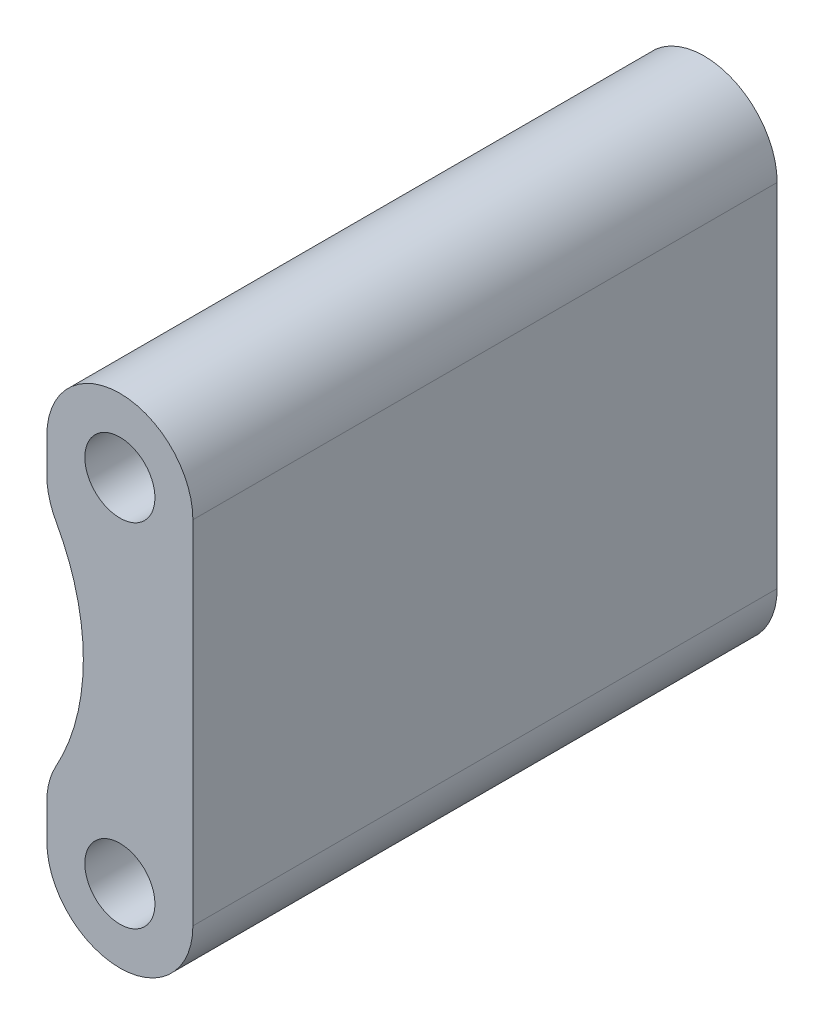
SolidWorks part; units mm, degrees
ref_plane "Front Plane" through (0, 0, 0) normal (0, 0, 1) x (1, 0, 0)
ref_plane "Top Plane" through (0, 0, 0) normal (0, 1, 0) x (1, 0, 0)
ref_plane "Right Plane" through (0, 0, 0) normal (1, 0, 0) x (0, 0, -1)
sketch "Sketch1" plane through (0, 0, 0) normal (0, 0, 1) x (1, 0, 0)
  line L0 (0, 22.9362) -> (0, 0) construction
  line L1 (0, 22.9362) -> (0, 0) construction
  line L2 (4.7625, 22.9362) -> (4.7625, 0)
  line L3 (-4.7625, 22.9362) -> (-4.7625, 0)
  circle A0 centre (0, 0) radius 2.286
  circle A1 centre (0, 22.9362) radius 2.286
  arc A2 (4.7625, 22.9362) -> (-4.7625, 22.9362) centre (0, 22.9362) ccw
  arc A3 (-4.7625, 0) -> (4.7625, 0) centre (0, 0) ccw
  point P5 (0, 11.4681)
  dimension "D1" = 4.572
  dimension "D3" = 4.7625
  dimension "D2" = 22.9362
extrude "Boss-Extrude1" add sketch "Sketch1" along normal blind 38.1
sketch "Sketch2" plane through (0, 0, 38.1) normal (0, 0, 1) x (1, 0, 0)
  line L0 (-4.7625, 22.9362) -> (-4.7625, 0) construction
  circle A0 centre (-16.67, 11.4681) radius 14.2875
  point P4 (-4.7625, 11.4681)
  dimension "D2" = 28.575
  dimension "D1" = 16.67
extrude "Cut-Extrude1" cut sketch "Sketch2" against normal through all
fillet "Fillet1" radius 4.7625 2 edges at (-4.7625, 3.5723, 19.05) (-4.7625, 19.3639, 19.05)
